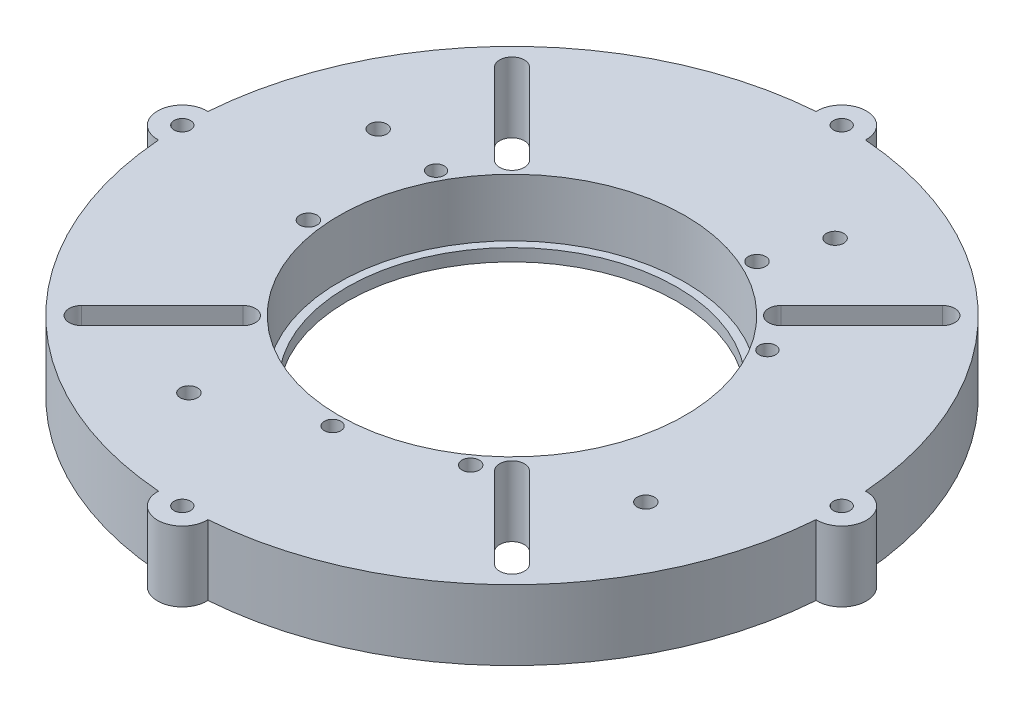
SolidWorks part; units mm, degrees
material "7075-T6 (SN)"
ref_plane "Front Plane" through (0, 0, 0) normal (0, 0, 1) x (1, 0, 0)
ref_plane "Top Plane" through (0, 0, 0) normal (0, 1, 0) x (1, 0, 0)
ref_plane "Right Plane" through (0, 0, 0) normal (1, 0, 0) x (0, 0, -1)
sketch "Sketch1" plane through (0, 0, 0) normal (0, 1, 0) x (1, 0, 0)
  circle A0 centre (0, 0) radius 20
  circle A1 centre (0, 0) radius 40
extrude "Boss-Extrude1" add sketch "Sketch1" along normal blind 8.5 contours A1 | A0
sketch "Sketch2" plane through (0, 8.5, 0) normal (0, 1, 0) x (1, 0, 0)
  circle A0 centre (40, 0) radius 3
  circle A1 centre (40, 0) radius 1
extrude "Cut-Extrude2" cut sketch "Sketch2" against normal through all contours A1
extrude "Boss-Extrude3" add sketch "Sketch2<6>" against normal blind 8.5
sketch "Sketch2<6>" plane through (0, 8.5, 0) normal (0, 1, 0) x (1, 0, 0) same geometry as "Sketch2"
pattern_circular "CirPattern1" count 4 over 360 about axis through (0, 8.5, 0) along (0, 1, 0) of "Cut-Extrude2", "Boss-Extrude3"
sketch "Sketch4" plane through (0, 8.5, 0) normal (0, 1, 0) x (1, 0, 0)
  line L0 (-26.1099, -26.1099) -> (-16.3165, -16.3165) construction
  line L1 (-27.1706, -25.0493) -> (-17.3771, -15.2558)
  line L2 (-25.0493, -27.1706) -> (-15.2558, -17.3771)
  line L3 (-21.2132, -21.2132) -> (0, 0) construction
  arc A0 (-27.1706, -25.0493) -> (-25.0493, -27.1706) centre (-26.1099, -26.1099) ccw
  arc A1 (-15.2558, -17.3771) -> (-17.3771, -15.2558) centre (-16.3165, -16.3165) ccw
  circle A2 centre (0, 0) radius 20 construction
  point P2 (-21.2132, -21.2132)
  dimension "D1" = 13.85
  dimension "D2" = 1.5
  dimension "D3" = 23.075
extrude "Cut-Extrude4" cut sketch "Sketch4" against normal through all
pattern_circular "CirPattern3" count 4 over 360 about axis through (0, 8.5, 0) along (0, 1, 0) of "Cut-Extrude4"
sketch "Sketch7" plane through (0, 8.5, 0) normal (0, 1, 0) x (1, 0, 0)
  circle A0 centre (0, 0) radius 21
extrude "Cut-Extrude5" cut sketch "Sketch7" against normal blind 7
sketch "Sketch8" plane through (0, 8.5, 0) normal (0, 1, 0) x (1, 0, 0)
  circle A0 centre (0.7201, -22.4885) radius 1
  circle A1 centre (19.1156, 11.8678) radius 1
  circle A2 centre (-19.8356, 10.6207) radius 1
extrude "Outer_Retainer_M2_Tapped_Envelope" cut sketch "Sketch8" against normal blind 4.3
sketch "Sketch9" plane through (0, 0, 0) normal (0, -1, 0) x (1, 0, 0)
  circle A0 centre (27.7164, 11.4805) radius 1
  circle A1 centre (-11.4805, 27.7164) radius 1
  circle A2 centre (-27.7164, -11.4805) radius 1
  circle A3 centre (11.4805, -27.7164) radius 1
extrude "RevB_Oldham_Four_M2_Blind_Thread_Major" cut sketch "Sketch9" against normal blind 5.8
sketch "Sketch10" plane through (0, 0, 0) normal (0, -1, 0) x (1, 0, 0)
  circle A0 centre (27.7164, 11.4805) radius 1.51
  circle A1 centre (-11.4805, 27.7164) radius 1.51
  circle A2 centre (-27.7164, -11.4805) radius 1.51
  circle A3 centre (11.4805, -27.7164) radius 1.51
extrude "RevB_Oldham_Four_D3p02_Pilot_Pockets" cut sketch "Sketch10" against normal blind 1.1
sketch "Sketch11" plane through (0, 8.5, 0) normal (0, 1, 0) x (1, 0, 0)
  circle A0 centre (-22.3798, -2.3226) radius 1.05
  circle A1 centre (13.2013, -18.2202) radius 1.05
  circle A2 centre (9.1785, 20.5428) radius 1.05
extrude "Bench_OuterRetainer_M2_Thread_Major_Envelope_3x_D2p1" cut sketch "Sketch11" against normal blind 4
sketch "Sketch12" plane through (0, 8.5, 0) normal (0, 1, 0) x (1, 0, 0)
  circle A0 centre (27.7164, -11.4805) radius 1.05
  circle A1 centre (-11.4805, -27.7164) radius 1.05
  circle A2 centre (-27.7164, 11.4805) radius 1.05
  circle A3 centre (11.4805, 27.7164) radius 1.05
extrude "Bench_Oldham_M2_Clearance_4x_D2p1" cut sketch "Sketch12" against normal blind 9
